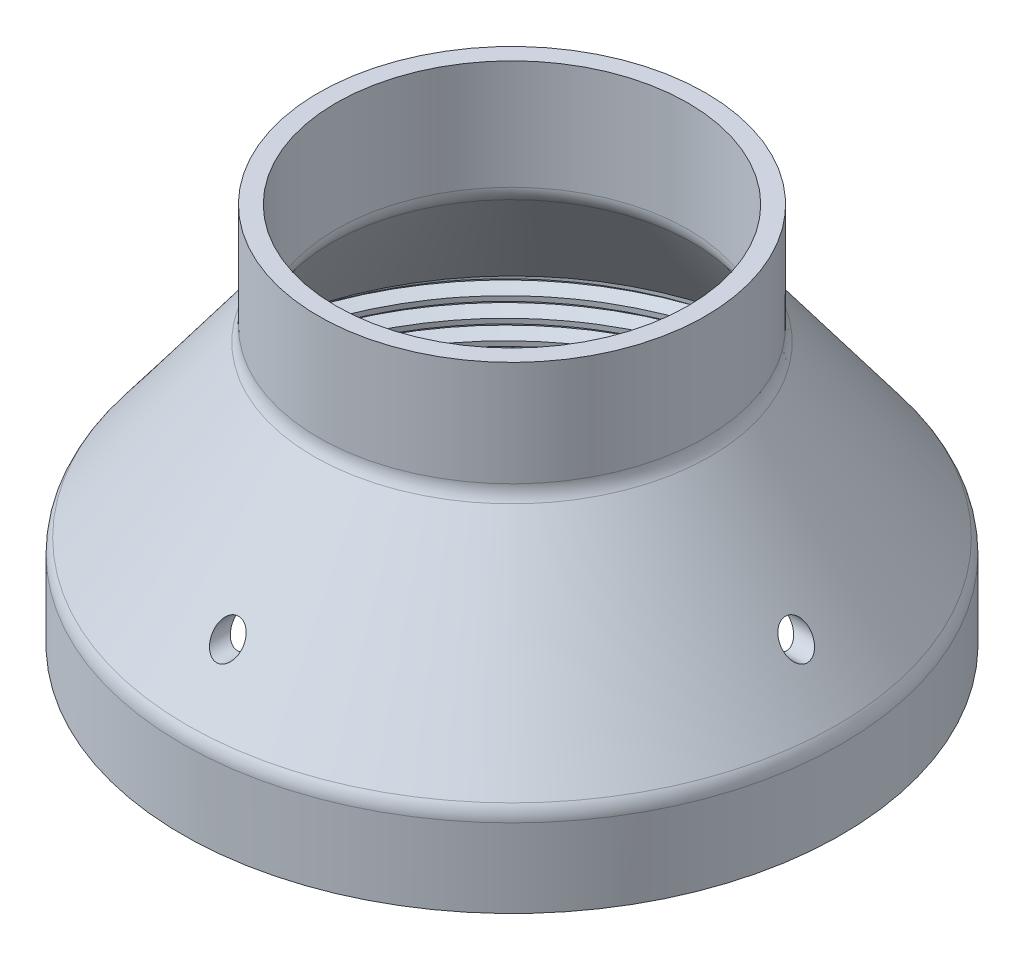
SolidWorks part; units mm, degrees
ref_plane "Front" through (0, 0, 0) normal (0, 0, 1) x (1, 0, 0)
ref_plane "Top" through (0, 0, 0) normal (0, 1, 0) x (1, 0, 0)
ref_plane "Right" through (0, 0, 0) normal (1, 0, 0) x (0, 0, -1)
sketch "Sketch1" plane through (0, 0, 0) normal (0, 0, 1) x (1, 0, 0)
  line L0 (35.687, 0) -> (35.687, 9.3438)
  line L1 (35.687, 9.3438) -> (20.955, 29.039)
  line L2 (20.955, 29.039) -> (20.955, 41.275)
  line L3 (20.955, 41.275) -> (19.05, 41.275)
  line L4 (19.05, 41.275) -> (19.05, 28.575)
  line L5 (19.05, 28.575) -> (30.9245, 12.7)
  line L6 (30.9245, 12.7) -> (30.9245, 0)
  line L7 (30.9245, 0) -> (35.687, 0)
  line L8 (0, 0) -> (0, 14.9629) construction
  line L9 (0, 0) -> (42.792, 0) construction
  dimension "D1" = 20.955
  dimension "D2" = 30.9245
  dimension "D3" = 12.7
  dimension "D4" = 19.05
  dimension "D5" = 12.7
  dimension "D6" = 1.8034
  dimension "D7" = 4.7625
  dimension "D8" = 15.875
revolve "Revolve1" add sketch "Sketch1" angle 360 about L8
chamfer "Chamfer1" distance 2.54 angle 45 1 edges at (0, 0, -30.9245)
thread "Thread1" pitch 2.1167 method cut profile "Thread Profile1" start angle 0, offset 0, length 12.7, pitch 2.1167, diameter 61.849
ref_plane "Plane1" through (-30.9245, 12.7, 0) normal (0, 0, 1) x (-1, 0, 0)
sketch "Thread Profile1" plane through (-30.9245, 12.7, 0) normal (0, 0, 1) x (-1, 0, 0)
  line L0 (0, 0) -> (0, 2.1167) construction
  line L1 (0, 0) -> (1.1457, 0.6615)
  line L2 (1.1457, 0.6615) -> (1.1457, 0.926)
  line L3 (1.1457, 0.926) -> (0, 1.5875)
  line L4 (1.1457, 0.7937) -> (0, 0.7937) construction
  line L11 (0, 0) -> (0, 1.5875)
  point P2 (0, 0)
  dimension "Pitch" = 2.1167
  dimension "Profile_Angle" = 60
  dimension "Profile_Land" = 0.2646
  dimension "Profile_Height" = 1.1457
fillet "Fillet1" radius 2.54 3 edges at (0, 29.039, -20.955) (0, 9.3438, -35.687) (0, 28.575, -19.05)
sketch "Sketch4" plane through (0, 41.275, 0) normal (0, 1, 0) x (1, 0, 0)
  circle A0 centre (0, 0) radius 66.7358
extrude "Cut-Extrude1" [suppressed] cut sketch "Sketch4" against normal blind 31.75
sketch "Sketch6" plane through (0, 0, 0) normal (0, 0, 1) x (1, 0, 0)
  line L0 (-35.687, 0) -> (35.687, 0) construction
  line L1 (0, 15.875) -> (0, 0) construction
  circle A0 centre (0, 15.875) radius 1.5875
  dimension "D1" = 3.175
  dimension "D2" = 15.875
extrude "Cut-Extrude2" cut sketch "Sketch6" against normal through all and the other way through all
pattern_circular "CirPattern1" count 4 over 360 about axis through (0, 41.275, 0) along (0, -1, 0) of "Cut-Extrude2"
